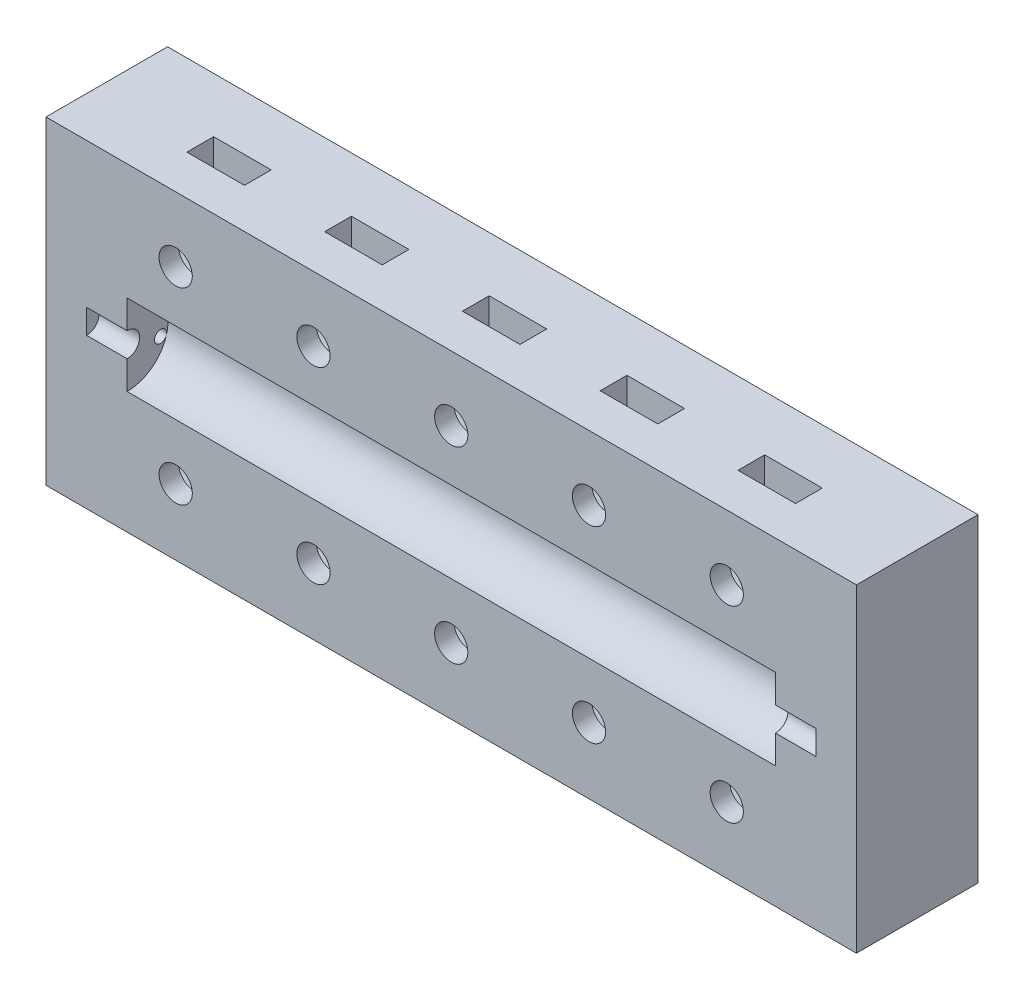
SolidWorks part; units mm, degrees
ref_plane "Ebene vorne" through (0, 0, 0) normal (0, 0, 1) x (1, 0, 0)
ref_plane "Ebene oben" through (0, 0, 0) normal (0, 1, 0) x (1, 0, 0)
ref_plane "Ebene rechts" through (0, 0, 0) normal (1, 0, 0) x (0, 0, -1)
sketch "Skizze2" plane through (0, 0, 0) normal (0, 0, 1) x (1, 0, 0)
  line L1 (0, 0) -> (100, 0)
  line L2 (0, 0) -> (0, 39.3642)
  line L3 (0, 39.3642) -> (100, 39.3642)
  line L4 (100, 0) -> (100, 39.3642)
  dimension "D1" = 39.3642
  dimension "D2" = 100
extrude "Aufsatz-Linear austragen1" add sketch "Skizze2" along normal blind 30
sketch "Skizze3" plane through (0, 0, 30) normal (0, 0, 1) x (1, 0, 0)
  line L0 (0, 19.6821) -> (100, 19.6821) construction
  line L1 (0, 39.3642) -> (0, 0) construction
  line L2 (100, 0) -> (100, 39.3642) construction
ref_plane "Ebene2" through (0, 19.7642, 0) normal (0, 1, 0) x (1, 0, 0)
sketch "Skizze9" plane through (0, 0, 30) normal (0, 0, 1) x (1, 0, 0)
  line L0 (50, 0) -> (50, 39.3642) construction
  line L1 (0, 0) -> (100, 0) construction
  line L2 (100, 39.3642) -> (0, 39.3642) construction
ref_plane "Ebene3" through (50, 0, 0) normal (-1, 0, 0) x (0, 0, 1)
sketch "Skizze10" plane through (50, 0, 0) normal (-1, 0, 0) x (0, 0, 1)
  line L0 (14.9458, 42.0451) -> (14.9458, -1.991) construction
  line L1 (-1.6741, 19.9497) -> (31.3778, 19.9497) construction
  circle A0 centre (14.9458, 20.027) radius 5
  dimension "D1" = 10
extrude "Schnitt-Linear austragen1" cut sketch "Skizze10" against normal blind 40 and the other way blind 40
ref_plane "Ebene4" through (90, 0, 0) normal (-1, 0, 0) x (0, 0, 1)
ref_plane "Ebene5" through (10, 0, 0) normal (-1, 0, 0) x (0, 0, 1)
sketch "Skizze17" plane through (90, 0, 0) normal (-1, 0, 0) x (0, 0, 1)
  circle A0 centre (14.9458, 20.027) radius 1.5
  dimension "D1" = 3
extrude "Schnitt-Linear austragen2" cut sketch "Skizze17" against normal blind 5
mirror "Spiegeln1" about plane through (50, 0, 0) normal (-1, 0, 0) of "Schnitt-Linear austragen2"
sketch "Skizze18" plane through (0, 39.3642, 0) normal (0, 1, 0) x (1, 0, 0)
  line L0 (100, -15) -> (0, -15) construction
  line L1 (100, -30) -> (100, 0) construction
ref_plane "Ebene6" through (0, 0, 15) normal (0, 0, -1) x (-1, 0, 0)
sketch "Skizze24" plane through (0, 0, 30) normal (0, 0, 1) x (1, 0, 0)
  line L0 (0, 39.3642) -> (0, 0) construction
  line L1 (100, 39.3642) -> (0, 39.3642) construction
  line L4 (100, 0) -> (100, 39.3642) construction
  circle A0 centre (16, 31.3642) radius 2.05
  circle A1 centre (33, 31.3642) radius 2.05
  circle A2 centre (50, 31.3642) radius 2.05
  circle A3 centre (67, 31.3642) radius 2.05
  circle A4 centre (84, 31.3642) radius 2.05
  dimension "D1" = 4.1
  dimension "D4" = 4.1
  dimension "D5" = 4.1
  dimension "D6" = 4.1
  dimension "D7" = 4.1
  dimension "D2" = 16
  dimension "D3" = 8
  dimension "D8" = 17
  dimension "D9" = 17
  dimension "D10" = 17
  dimension "D11" = 17
  dimension "D12" = 16
extrude "Schnitt-Linear austragen4" cut sketch "Skizze24" against normal through all
mirror "Spiegeln4" about plane through (0, 19.7642, 0) normal (0, 1, 0) of "Schnitt-Linear austragen4"
sketch "Skizze41" plane through (0, 0, 30) normal (0, 0, 1) x (1, 0, 0)
  circle A0 centre (16, 31.3642) radius 3.55
  dimension "D1" = 7.1
extrude "Schnitt-Linear austragen11" cut sketch "Skizze41" against normal blind 4.2
pattern_linear "Lineares Muster5" count 5 spacing 17 along (1, 0, 0) of "Schnitt-Linear austragen11"
mirror "Spiegeln9" about plane through (0, 19.7642, 0) normal (0, 1, 0) of "Lineares Muster5"
sketch "Skizze28" plane through (0, 0, 0) normal (0, -1, 0) x (-1, 0, 0)
  line L4 (-12.45, -6.7653) -> (-19.55, -6.7653)
  line L5 (-12.45, -6.7653) -> (-12.45, -10.0653)
  line L6 (-12.45, -10.0653) -> (-19.55, -10.0653)
  line L7 (-19.55, -6.7653) -> (-19.55, -10.0653)
  point P3 (-16, -2)
  point P7 (-16, -6.7653)
  dimension "D1" = 7.1
  dimension "D2" = 3.55
  dimension "D3" = 3.3
  dimension "D4" = 7.1
extrude "Schnitt-Linear austragen5" cut sketch "Skizze28" against normal blind 7.96
sketch "Skizze22" plane through (0, 0, 0) normal (-1, 0, 0) x (0, 0, 1)
  line L0 (30, 39.3642) -> (0, 39.3642) construction
  line L1 (0, 0) -> (15, 0)
  line L2 (0, 0) -> (0, 39.3642)
  line L3 (0, 39.3642) -> (15, 39.3642)
  line L5 (15, 39.3642) -> (34.4957, 39.3642)
  line L6 (15, 39.3642) -> (15, -0.6358)
  line L7 (15, -0.6358) -> (34.4957, -0.6358)
  line L8 (34.4957, 39.3642) -> (34.4957, -0.6358)
  dimension "D1" = 40
sketch "Skizze32" plane through (100, 0, 0) normal (1, 0, 0) x (0, 0, -1)
  line L0 (-8.4153, 7.96) -> (-8.4153, 0) construction
  line L1 (-6.7653, 7.96) -> (-10.0653, 7.96) construction
  line L2 (-30, 0) -> (0, 0) construction
  line L3 (-8.4153, 0) -> (-8.4153, 41.7817) construction
ref_plane "Ebene7" through (0, 0, 8.4) normal (0, 0, -1) x (-1, 0, 0)
sketch "Skizze33" plane through (0, 0, 8.4) normal (0, 0, -1) x (-1, 0, 0)
  line L0 (-16, 8.1642) -> (-16, 39.3642) construction
  line L1 (-100, 39.3642) -> (0, 39.3642) construction
  line L2 (-16, 39.3642) -> (-16, 0) construction
  line L3 (0, 0) -> (-100, 0) construction
ref_plane "Ebene8" through (16, 0, 0) normal (-1, 0, 0) x (0, 0, 1)
sketch "Skizze34" plane through (0, 0, 8.4) normal (0, 0, -1) x (-1, 0, 0)
  line L1 (-16, 12.2056) -> (-19.5, 10.1849)
  line L2 (-19.5, 10.1849) -> (-19.5, 6.1434)
  line L3 (-19.5, 6.1434) -> (-16, 4.1227)
  line L4 (-16, 4.1227) -> (-12.5, 6.1434)
  line L5 (-12.5, 6.1434) -> (-12.5, 10.1849)
  line L6 (-12.5, 10.1849) -> (-16, 12.2056)
  circle A0 centre (-16, 8.1642) radius 3.5 construction
  dimension "D1" = 7
extrude "Schnitt-Linear austragen8" cut sketch "Skizze34" against normal blind 4.2 and the other way blind 1.65
pattern_linear "Lineares Muster3" count 5 spacing 17 along (1, 0, 0) of "Schnitt-Linear austragen8"
pattern_linear "Lineares Muster4" count 5 spacing 17 along (1, 0, 0) of "Schnitt-Linear austragen5"
mirror "Spiegeln6" about plane through (0, 19.7642, 0) normal (0, 1, 0) of "Schnitt-Linear austragen8"
mirror "Spiegeln7" about plane through (0, 19.7642, 0) normal (0, 1, 0) of "Lineares Muster3"
mirror "Spiegeln8" about plane through (0, 19.7642, 0) normal (0, 1, 0) of "Lineares Muster4"
sketch "Skizze35" plane through (0, 0, 30) normal (0, 0, 1) x (1, 0, 0)
  line L0 (89.9018, 21.3451) -> (89.9018, 39.3769) construction
  line L1 (89.9018, 39.3769) -> (89.9018, 0) construction
  line L2 (0, 0) -> (100, 0) construction
ref_plane "Ebene9" through (90, 0, 0) normal (1, 0, 0) x (0, 0, -1)
sketch "Skizze36" plane through (90, 0, 0) normal (1, 0, 0) x (0, 0, -1)
  line L0 (-20.1004, 18.2046) -> (-18.9246, 18.6336)
  circle A0 centre (-18.9246, 18.6336) radius 0.75
  point P3 (-19.5125, 18.4191)
  point P4 (-18.9246, 18.6336)
  dimension "D1" = 1.5
sketch "Skizze37" plane through (100, 0, 0) normal (1, 0, 0) x (0, 0, -1)
  circle A0 centre (-18.9246, 18.6336) radius 0.7369
extrude "Schnitt-Linear austragen9" cut sketch "Skizze37" against normal through all
sketch "Skizze40" plane through (100, 0, 0) normal (1, 0, 0) x (0, 0, -1)
  circle A0 centre (-18.9246, 18.6336) radius 2
  dimension "D1" = 4
extrude "Schnitt-Linear austragen10" cut sketch "Skizze40" against normal blind 6
sketch "Skizze42" plane through (0, 0, 0) normal (-1, 0, 0) x (0, 0, 1)
  line L0 (10.1439, 18.6336) -> (10.8642, 18.8426) construction
  circle A0 centre (14.9458, 20.027) radius 5 construction
  circle A1 centre (10.8642, 18.8426) radius 0.75
  dimension "D1" = 0.75
extrude "Schnitt-Linear austragen12" cut sketch "Skizze42" against normal blind 10
fillet "Verrundung1" radius 1 1 edges at (94, 18.6336, 18.1877)
fillet "Verrundung2" radius 1 1 edges at (90, 18.6336, 19.6615)
sketch "Skizze46" plane through (100, 0, 0) normal (1, 0, 0) x (0, 0, -1)
  line L1 (-15, 39.3642) -> (-30, 39.3642)
  line L2 (-15, 39.3642) -> (-15, 0)
  line L3 (-15, 0) -> (-30, 0)
  line L4 (-30, 39.3642) -> (-30, 0)
extrude "Schnitt-Linear austragen15" cut sketch "Skizze46" against normal blind 100
